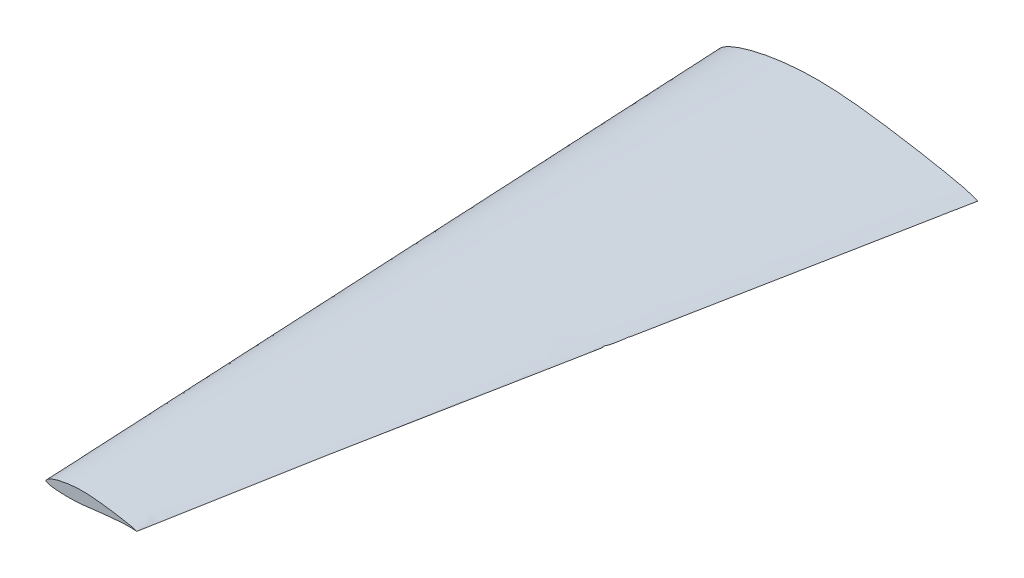
SolidWorks part; units mm, degrees
ref_plane "Front Plane" through (0, 0, 0) normal (0, 0, 1) x (1, 0, 0)
ref_plane "Top Plane" through (0, 0, 0) normal (0, 1, 0) x (1, 0, 0)
ref_plane "Right Plane" through (0, 0, 0) normal (1, 0, 0) x (0, 0, -1)
curve "Curve1"
  spline degree 3 poles (0.9921, 0.0008, 0) (1.0019, -0.0008, 0) (0.9929, 0.0016, 0) (0.9861, 0.0043, 0) (0.9706, 0.0096, 0) (0.9519, 0.0152, 0) (0.9278, 0.021, 0) (0.8992, 0.0273, 0) (0.8662, 0.0341, 0) (0.8293, 0.0413, 0) (0.789, 0.0488, 0) (0.746, 0.0564, 0) (0.7007, 0.0641, 0) (0.6538, 0.0714, 0) (0.6058, 0.0784, 0) (0.5573, 0.0846, 0) (0.5088, 0.0898, 0) (0.4609, 0.0938, 0) (0.4138, 0.0961, 0) (0.3679, 0.0966, 0) (0.3232, 0.0952, 0) (0.2801, 0.092, 0) (0.2388, 0.0874, 0) (0.1997, 0.0815, 0) (0.1631, 0.0746, 0) (0.1296, 0.0669, 0) (0.0993, 0.0585, 0) (0.0726, 0.0496, 0) (0.0499, 0.0404, 0) (0.0312, 0.031, 0) (0.0168, 0.0217, 0) (0.0085, 0.0145, 0) (0.0039, 0.009, 0) (0.0018, 0.0058, 0) (0.0004, 0.0024, 0) (0, 0.0003, 0) (0, -0.0012, 0) (0.0006, -0.0026, 0) (0.002, -0.0043, 0) (0.0049, -0.007, 0) (0.0107, -0.0108, 0) (0.0215, -0.0156, 0) (0.0378, -0.0206, 0) (0.0598, -0.0253, 0) (0.0864, -0.0294, 0) (0.1174, -0.033, 0) (0.1523, -0.036, 0) (0.1908, -0.0383, 0) (0.2323, -0.0397, 0) (0.2764, -0.0402, 0) (0.3228, -0.0395, 0) (0.3711, -0.0373, 0) (0.4212, -0.0335, 0) (0.4729, -0.0284, 0) (0.526, -0.0227, 0) (0.5798, -0.0169, 0) (0.6336, -0.0114, 0) (0.6866, -0.0064, 0) (0.7378, -0.0023, 0) (0.7866, 0.0009, 0) (0.832, 0.0031, 0) (0.8733, 0.0042, 0) (0.9096, 0.0045, 0) (0.9406, 0.0038, 0) (0.9645, 0.0029, 0) (0.984, 0.0013, 0) (0.9921, 0.0008, 0) (1.0019, -0.0008, 0) (0.9929, 0.0016, 0) knots -0.016161 -0.007282 -0.001839 0 0.00178 0.006777 0.014308 0.024046 0.036116 0.050547 0.06713 0.085624 0.105767 0.127282 0.149864 0.17323 0.197069 0.221103 0.245052 0.268663 0.291773 0.314299 0.336178 0.357377 0.377792 0.397225 0.415489 0.432417 0.447849 0.461651 0.473687 0.483898 0.492263 0.498797 0.499955 0.502811 0.504371 0.50536 0.505925 0.506503 0.507535 0.509205 0.512345 0.517665 0.526422 0.537425 0.550643 0.565966 0.583206 0.602155 0.622587 0.644255 0.666998 0.690703 0.715307 0.740824 0.767084 0.793717 0.820331 0.846519 0.871863 0.895937 0.918335 0.938667 0.956573 0.971715 0.983839 0.992718 0.998161 1 1.00178 1.006777 1.014308 periodic
sketch "Sketch1" plane through (0, 0, 0) normal (0, 0, 1) x (1, 0, 0)
  line L0 (1122.2059, -30.8288) -> (-1162.7941, -35.0845) construction
  spline S1 degree 3 poles (1104.1363, -28.0222) (1126.6295, -31.7875) (1105.8826, -26.3024) (1090.4575, -20.1288) (1054.9513, -7.9956) (1012.296, 4.6638) (957.0478, 17.8508) (891.7164, 32.0367) (816.2153, 47.3864) (731.9108, 63.6705) (639.9041, 80.612) (541.5101, 97.9168) (438.0076, 115.0958) (330.7593, 131.7488) (221.0675, 147.3336) (110.2357, 161.251) (-0.493, 172.9975) (-110.0556, 181.8587) (-217.6516, 186.9061) (-322.6724, 187.859) (-424.6755, 184.4831) (-523.1626, 176.9995) (-617.5035, 166.1709) (-706.8843, 152.6667) (-790.3524, 136.737) (-867.0563, 118.889) (-936.2082, 99.5088) (-997.0691, 79.0242) (-1049.0447, 57.9028) (-1091.6336, 36.4479) (-1124.4686, 15.1943) (-1143.3869, -1.4067) (-1153.8659, -14.0298) (-1158.6984, -21.3016) (-1161.9612, -29.0988) (-1162.8988, -33.8887) (-1162.7223, -37.2464) (-1161.3764, -40.4052) (-1158.2301, -44.4654) (-1151.5185, -50.6376) (-1138.2079, -59.2164) (-1113.635, -70.0567) (-1076.2399, -81.3981) (-1026.0446, -92.1031) (-965.2298, -101.4019) (-894.4776, -109.4657) (-814.6314, -116.0953) (-726.7099, -121.1028) (-631.8133, -124.2931) (-530.9633, -125.2112) (-425.0342, -123.2363) (-314.6436, -117.9744) (-200.1569, -109.1265) (-81.9663, -97.1903) (39.2548, -83.9633) (162.1641, -70.4688) (285.0306, -57.6215) (406.0083, -46.0046) (523.1884, -36.2734) (634.6311, -28.7415) (738.3789, -23.5277) (832.7109, -20.7776) (915.5317, -20.0924) (986.36, -21.3847) (1040.9806, -23.338) (1085.6437, -26.9173) (1104.1363, -28.0222) (1126.6295, -31.7875) (1105.8826, -26.3024) knots -0.016161 -0.007282 -0.001839 0 0.00178 0.006777 0.014308 0.024046 0.036116 0.050547 0.06713 0.085624 0.105767 0.127282 0.149864 0.17323 0.197069 0.221103 0.245052 0.268663 0.291773 0.314299 0.336178 0.357377 0.377792 0.397225 0.415489 0.432417 0.447849 0.461651 0.473687 0.483898 0.492263 0.498797 0.499955 0.502811 0.504371 0.50536 0.505925 0.506503 0.507535 0.509205 0.512345 0.517665 0.526422 0.537425 0.550643 0.565966 0.583206 0.602155 0.622587 0.644255 0.666998 0.690703 0.715307 0.740824 0.767084 0.793717 0.820331 0.846519 0.871863 0.895937 0.918335 0.938667 0.956573 0.971715 0.983839 0.992718 0.998161 1 1.00178 1.006777 1.014308 only from (1122.2059, -30.8288) to (1122.2059, -30.8288)
  dimension "D1" = 2285
ref_plane "Plane1" through (0, 0, 6200) normal (0, 0, 1) x (1, 0, 0)
ref_plane "Plane3" through (0, -35.0845, 0) normal (0, 1, 0) x (1, 0, 0)
sketch "Sketch4" plane through (0, -35.0845, 0) normal (0, 1, 0) x (1, 0, 0)
  line L1 (1122.2059, 0) -> (-1162.7941, 0) construction
  line L2 (-172.1886, -6200) -> (172.1886, -6200) construction
  line L4 (-1162.7941, 0) -> (-862.7941, -6200)
sketch "Sketch5" plane through (0, 0, 6200) normal (0, 0, 1) x (1, 0, 0)
  line L0 (-62.749, -35.2354) -> (-862.7688, -35.3009) construction
  spline S1 degree 3 poles (-69.0897, -34.3504) (-61.22, -35.5469) (-68.4893, -33.741) (-73.9048, -31.6671) (-86.3598, -27.6181) (-101.3126, -23.4229) (-120.663, -19.1093) (-143.5377, -14.4998) (-169.9677, -9.5373) (-199.4749, -4.2947) (-231.6736, 1.1372) (-266.1033, 6.6624) (-302.3153, 12.1171) (-339.8318, 17.3686) (-378.1955, 22.2345) (-416.9483, 26.5125) (-455.6538, 30.0335) (-493.9373, 32.5536) (-531.5145, 33.7529) (-568.1715, 33.5367) (-603.7528, 31.8256) (-638.0855, 28.6992) (-670.9538, 24.4271) (-702.0769, 19.2472) (-731.124, 13.2516) (-757.8002, 6.6219) (-781.8329, -0.5031) (-802.9662, -7.9701) (-820.9952, -15.6131) (-835.7466, -23.3233) (-847.0949, -30.9123) (-853.6106, -36.8049) (-857.2018, -41.2651) (-858.8503, -43.8282) (-859.9483, -46.5664) (-860.2505, -48.243) (-860.1714, -49.4139) (-859.6851, -50.5093) (-858.5659, -51.9099) (-856.1913, -54.0289) (-851.5011, -56.9533) (-842.8685, -60.6082) (-829.7584, -64.3709) (-812.1844, -67.8447) (-790.9116, -70.7722) (-766.1771, -73.2167) (-738.2762, -75.1133) (-707.5656, -76.4015) (-674.4302, -77.0191) (-639.2289, -76.8125) (-602.2702, -75.5698) (-563.7715, -73.1566) (-523.8621, -69.4706) (-482.6761, -64.6873) (-440.4393, -59.4377) (-397.6147, -54.086) (-354.8016, -48.9603) (-312.6413, -44.2739) (-271.7964, -40.2655) (-232.9425, -37.0546) (-196.7619, -34.6929) (-163.8546, -33.2402) (-134.9538, -32.5684) (-110.2281, -32.6493) (-91.1554, -33.0456) (-75.5494, -34.0614) (-69.0897, -34.3504) (-61.22, -35.5469) (-68.4893, -33.741) knots -0.016161 -0.007282 -0.001839 0 0.00178 0.006777 0.014308 0.024046 0.036116 0.050547 0.06713 0.085624 0.105767 0.127282 0.149864 0.17323 0.197069 0.221103 0.245052 0.268663 0.291773 0.314299 0.336178 0.357377 0.377792 0.397225 0.415489 0.432417 0.447849 0.461651 0.473687 0.483898 0.492263 0.498797 0.499955 0.502811 0.504371 0.50536 0.505925 0.506503 0.507535 0.509205 0.512345 0.517665 0.526422 0.537425 0.550643 0.565966 0.583206 0.602155 0.622587 0.644255 0.666998 0.690703 0.715307 0.740824 0.767084 0.793717 0.820331 0.846519 0.871863 0.895937 0.918335 0.938667 0.956573 0.971715 0.983839 0.992718 0.998161 1 1.00178 1.006777 1.014308 only from (-62.7688, -35.2354) to (-62.7688, -35.2354)
  dimension "D1" = 800
loft "Loft5" add profiles "Sketch1", "Sketch5" connector at (-829.2128, 127.5517, 0) connector at (-729.5824, 13.4038, 6200)
sketch "Sketch9" plane through (0, 0, 0) normal (0, 0, -1) x (-1, 0, 0)
  line L1 (513.5943, 97.9459) -> (666.6195, 97.9459)
  line L2 (513.5943, 97.9459) -> (513.5943, -16.278)
  line L3 (513.5943, -16.278) -> (666.6195, -16.278)
  line L4 (666.6195, 97.9459) -> (666.6195, -16.278)
  line L5 (513.5943, 97.9459) -> (666.6195, -16.278) construction
  line L6 (513.5943, -16.278) -> (666.6195, 97.9459) construction
  point P0 (590.1069, 40.8339)
extrude "Boss-Extrude1" add sketch "Sketch9" along normal blind 30
sketch "Sketch14" plane through (0, 0, 0) normal (0, 0, -1) x (-1, 0, 0)
  spline S0 degree 3 poles (-1105.8826, -26.3024) (-1126.6295, -31.7875) (-1104.1363, -28.0222) (-1085.6437, -26.9173) (-1040.9806, -23.338) (-986.36, -21.3847) (-915.5317, -20.0924) (-832.7109, -20.7776) (-738.3789, -23.5277) (-634.6311, -28.7415) (-523.1884, -36.2734) (-406.0083, -46.0046) (-285.0306, -57.6215) (-162.1641, -70.4688) (-39.2548, -83.9633) (81.9663, -97.1903) (200.1569, -109.1265) (314.6436, -117.9744) (425.0342, -123.2363) (530.9633, -125.2112) (631.8133, -124.2931) (726.7099, -121.1028) (814.6314, -116.0953) (894.4776, -109.4657) (965.2298, -101.4019) (1026.0446, -92.1031) (1076.2399, -81.3981) (1113.635, -70.0567) (1138.2079, -59.2164) (1151.5185, -50.6376) (1158.2301, -44.4654) (1161.3764, -40.4052) (1162.7223, -37.2464) (1162.8988, -33.8887) (1161.9612, -29.0988) (1158.6984, -21.3016) (1153.8659, -14.0298) (1143.3869, -1.4067) (1124.4686, 15.1943) (1091.6336, 36.4479) (1049.0447, 57.9028) (997.0691, 79.0242) (936.2082, 99.5088) (867.0563, 118.889) (790.3524, 136.737) (706.8843, 152.6667) (617.5035, 166.1709) (523.1626, 176.9995) (424.6755, 184.4831) (322.6724, 187.859) (217.6516, 186.9061) (110.0556, 181.8587) (0.493, 172.9975) (-110.2357, 161.251) (-221.0675, 147.3336) (-330.7593, 131.7488) (-438.0076, 115.0958) (-541.5101, 97.9168) (-639.9041, 80.612) (-731.9108, 63.6705) (-816.2153, 47.3864) (-891.7164, 32.0367) (-957.0478, 17.8508) (-1012.296, 4.6638) (-1054.9513, -7.9956) (-1090.4575, -20.1288) (-1105.8826, -26.3024) (-1126.6295, -31.7875) (-1104.1363, -28.0222) knots -0.014308 -0.006777 -0.00178 0 0.001839 0.007282 0.016161 0.028285 0.043427 0.061333 0.081665 0.104063 0.128137 0.153481 0.179669 0.206283 0.232916 0.259176 0.284693 0.309297 0.333002 0.355745 0.377413 0.397845 0.416794 0.434034 0.449357 0.462575 0.473578 0.482335 0.487655 0.490795 0.492465 0.493497 0.494075 0.49464 0.495629 0.497189 0.500045 0.501203 0.507737 0.516102 0.526313 0.538349 0.552151 0.567583 0.584511 0.602775 0.622208 0.642623 0.663822 0.685701 0.708227 0.731337 0.754948 0.778897 0.802931 0.82677 0.850136 0.872718 0.894233 0.914376 0.93287 0.949453 0.963884 0.975954 0.985692 0.993223 0.99822 1 1.001839 1.007282 1.016161 only from (-1122.2059, -30.8288) to (-1122.2059, -30.8288) construction
  point P0 (1162.7705, -34.2556)
  point P1 (975.8068, -63.107)
